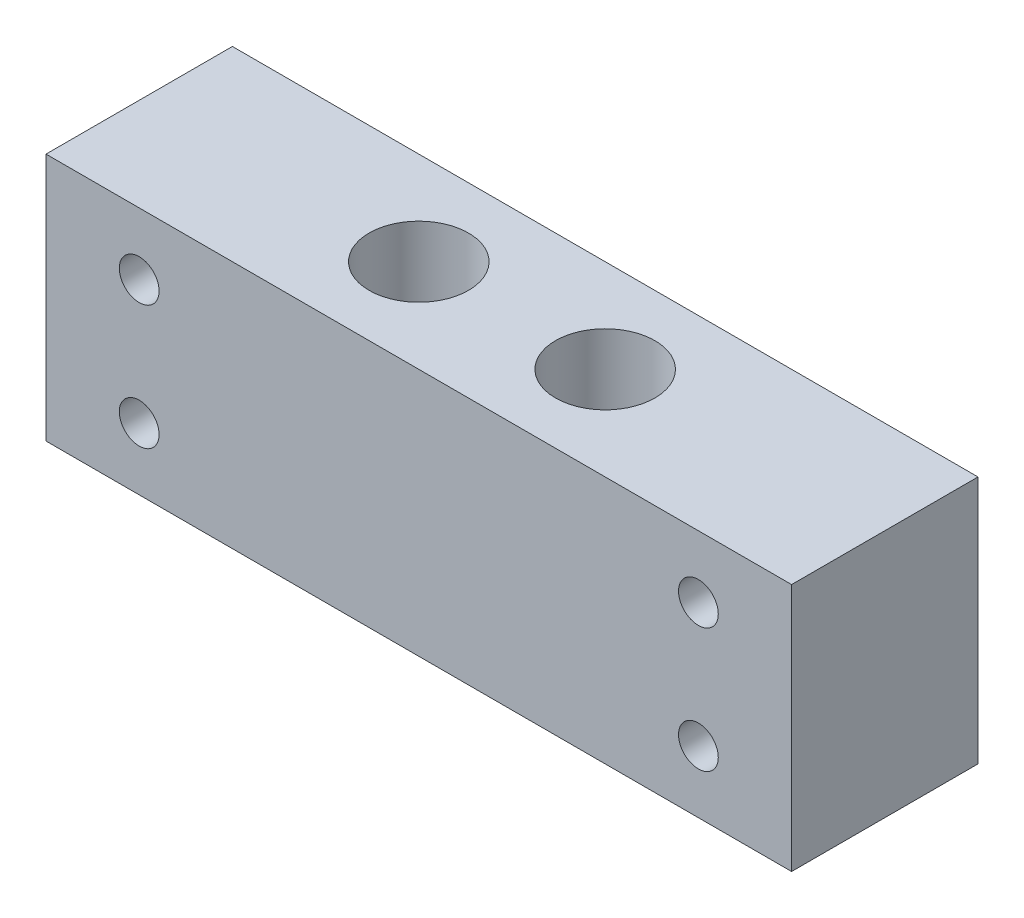
SolidWorks part; units mm, degrees
ref_plane "Front Plane" through (0, 0, 0) normal (0, 0, 1) x (1, 0, 0)
ref_plane "Top Plane" through (0, 0, 0) normal (0, 1, 0) x (1, 0, 0)
ref_plane "Right Plane" through (0, 0, 0) normal (1, 0, 0) x (0, 0, -1)
sketch "Sketch2" plane through (0, 0, 0) normal (0, 1, 0) x (1, 0, 0)
  line L0 (0, 0) -> (-7.5, 0) construction
  line L1 (0, 0) -> (7.5, 0) construction
  line L3 (15, -7.5) -> (-15, -7.5)
  line L4 (15, -7.5) -> (15, 7.5)
  line L5 (15, 7.5) -> (-15, 7.5)
  line L6 (-15, -7.5) -> (-15, 7.5)
  line L7 (15, -7.5) -> (-15, 7.5) construction
  line L8 (15, 7.5) -> (-15, -7.5) construction
  line L9 (-15, 7.5) -> (-30, 7.5)
  line L10 (-15, 7.5) -> (-15, -7.5)
  line L11 (-15, -7.5) -> (-30, -7.5)
  line L12 (-30, 7.5) -> (-30, -7.5)
  line L13 (15, 7.5) -> (30, 7.5)
  line L14 (15, 7.5) -> (15, -7.5)
  line L15 (15, -7.5) -> (30, -7.5)
  line L16 (30, 7.5) -> (30, -7.5)
  circle A0 centre (-7.5, 0) radius 4
  circle A1 centre (7.5, 0) radius 4
  dimension "D3" = 8
  dimension "D4" = 8
  dimension "D1" = 7.5
  dimension "D2" = 7.5
  dimension "D5" = 15
  dimension "D6" = 30
  dimension "D7" = 15
  dimension "D8" = 15
  dimension "D9" = 15
  dimension "D10" = 15
extrude "Boss-Extrude1" add sketch "Sketch2" along normal blind 10 contours L9 L12 L11 L6 | L6 L3 L4 L5 A1 A0 | L16 L13 L4 L15 region at (0, 0, 0) region at (22.5, 0, 0) region at (-22.5, 0, 0)
extrude "Boss-Extrude2" add sketch "Sketch2<3>" against normal blind 10 contours L9 L12 L11 L6 | L6 L3 L4 L5 A1 A0 | A0 | A1 | L16 L13 L4 L15 region at (0, 0, 0) region at (22.5, 0, 0) region at (-22.5, 0, 0) region at (-7.5, 0, 0) region at (7.5, 0, 0)
sketch "Sketch2<3>" plane through (0, 0, 0) normal (0, 1, 0) x (1, 0, 0) same geometry as "Sketch2"
sketch "Sketch4" plane through (0, 0, 7.5) normal (0, 0, 1) x (1, 0, 0)
  line L0 (-30, 0) -> (-22.5, 0) construction
  line L1 (-30, 10) -> (-30, -10) construction
  line L2 (30, 0) -> (22.5, 0) construction
  line L3 (30, 10) -> (30, -10) construction
  line L4 (-22.5, -5) -> (-22.5, 5) construction
  line L5 (22.5, -5) -> (22.5, 5) construction
  line L7 (-22.5, 8.4352) -> (-25.475, 6.7176)
  line L8 (-25.475, 6.7176) -> (-25.475, 3.2824)
  line L9 (-25.475, 3.2824) -> (-22.5, 1.5648)
  line L10 (-22.5, 1.5648) -> (-19.525, 3.2824)
  line L11 (-19.525, 3.2824) -> (-19.525, 6.7176)
  line L12 (-19.525, 6.7176) -> (-22.5, 8.4352)
  line L13 (22.5, 8.4352) -> (19.525, 6.7176)
  line L14 (19.525, 6.7176) -> (19.525, 3.2824)
  line L15 (19.525, 3.2824) -> (22.5, 1.5648)
  line L16 (22.5, 1.5648) -> (25.475, 3.2824)
  line L17 (25.475, 3.2824) -> (25.475, 6.7176)
  line L18 (25.475, 6.7176) -> (22.5, 8.4352)
  line L19 (-22.5, -8.4352) -> (-19.525, -6.7176)
  line L20 (22.5, -8.4352) -> (25.475, -6.7176)
  line L21 (25.475, -6.7176) -> (25.475, -3.2824)
  line L22 (25.475, -3.2824) -> (22.5, -1.5648)
  line L23 (22.5, -1.5648) -> (19.525, -3.2824)
  line L24 (19.525, -3.2824) -> (19.525, -6.7176)
  line L25 (19.525, -6.7176) -> (22.5, -8.4352)
  line L26 (-19.525, -6.7176) -> (-19.525, -3.2824)
  line L27 (-19.525, -3.2824) -> (-22.5, -1.5648)
  line L28 (-22.5, -1.5648) -> (-25.475, -3.2824)
  line L29 (-25.475, -3.2824) -> (-25.475, -6.7176)
  line L30 (-25.475, -6.7176) -> (-22.5, -8.4352)
  circle A0 centre (22.5, 5) radius 1.6
  circle A1 centre (22.5, -5) radius 1.6
  circle A2 centre (-22.5, -5) radius 1.6
  circle A3 centre (-22.5, 5) radius 1.6
  circle A4 centre (-22.5, 5) radius 2.975 construction
  circle A5 centre (22.5, 5) radius 2.975 construction
  circle A6 centre (22.5, -5) radius 2.975 construction
  circle A7 centre (-22.5, -5) radius 2.975 construction
  point P12 (-22.5, 0)
  point P15 (22.5, 0)
  dimension "D5" = 3.2
  dimension "D6" = 3.2
  dimension "D7" = 3.2
  dimension "D8" = 3.2
  dimension "D9" = 5.95
  dimension "D10" = 5.95
  dimension "D11" = 5.95
  dimension "D12" = 5.95
  dimension "D1" = 7.5
  dimension "D2" = 7.5
  dimension "D3" = 10
  dimension "D4" = 10
extrude "Cut-Extrude1" cut sketch "Sketch4" against normal through all contours A2 | A3 | A0 | A1 region at (22.5, 5, 7.5) region at (22.5, -5, 7.5) region at (-22.5, -5, 7.5) region at (-22.5, 5, 7.5)
extrude "Cut-Extrude2" cut sketch "Sketch4<3>" against normal blind 2.5 from offset 6.25 offset against normal yes
sketch "Sketch4<3>" plane through (0, 0, 7.5) normal (0, 0, 1) x (1, 0, 0) same geometry as "Sketch4"
